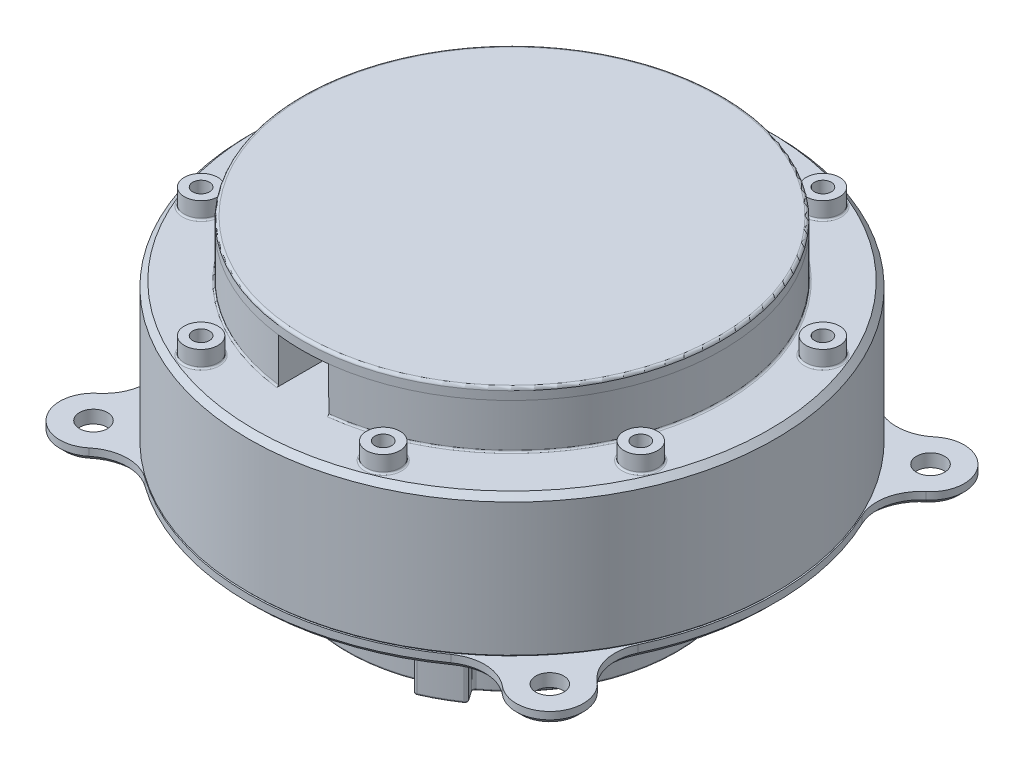
SolidWorks part; units mm, degrees
material "6061 合金"
ref_plane "前视基准面" through (0, 0, 0) normal (0, 0, 1) x (1, 0, 0)
ref_plane "上视基准面" through (0, 0, 0) normal (0, 1, 0) x (1, 0, 0)
ref_plane "右视基准面" through (0, 0, 0) normal (1, 0, 0) x (0, 0, -1)
sketch "草图1" plane through (0, 0, 0) normal (0, 1, 0) x (1, 0, 0)
  line L1 (16.264, -39.2649) -> (39.2649, -16.264) construction
  line L2 (39.2649, -16.264) -> (39.2649, 16.264) construction
  line L3 (39.2649, 16.264) -> (16.264, 39.2649) construction
  line L4 (16.264, 39.2649) -> (-16.264, 39.2649) construction
  line L5 (-16.264, 39.2649) -> (-39.2649, 16.264) construction
  line L6 (-39.2649, 16.264) -> (-39.2649, -16.264) construction
  line L7 (-39.2649, -16.264) -> (-16.264, -39.2649) construction
  line L8 (-16.264, -39.2649) -> (16.264, -39.2649) construction
  circle A0 centre (0, 0) radius 42.5 construction
  circle A1 centre (0, 0) radius 47
  circle A2 centre (0, 0) radius 39.2649 construction
  circle A3 centre (-16.264, 39.2649) radius 1.5
  circle A4 centre (16.264, 39.2649) radius 1.5
  circle A5 centre (39.2649, 16.264) radius 1.5
  circle A6 centre (39.2649, -16.264) radius 1.5
  circle A7 centre (16.264, -39.2649) radius 1.5
  circle A8 centre (-16.264, -39.2649) radius 1.5
  circle A9 centre (-39.2649, -16.264) radius 1.5
  circle A10 centre (-39.2649, 16.264) radius 1.5
  dimension "D1" = 85
  dimension "D2" = 94
  dimension "D3" = 3
extrude "凸台-拉伸1" add sketch "草图1" along normal blind 25
sketch "草图2" plane through (0, 25, 0) normal (0, 1, 0) x (1, 0, 0)
  circle A0 centre (-16.264, 39.2649) radius 3
  circle A1 centre (16.264, 39.2649) radius 1.5
  circle A2 centre (16.264, 39.2649) radius 1.5
  circle A3 centre (-16.264, 39.2649) radius 1.5
  circle A4 centre (-16.264, 39.2649) radius 1.5
  circle A5 centre (39.2649, 16.264) radius 1.5
  circle A6 centre (39.2649, 16.264) radius 1.5
  circle A7 centre (39.2649, -16.264) radius 1.5
  circle A8 centre (39.2649, -16.264) radius 1.5
  circle A9 centre (16.264, -39.2649) radius 1.5
  circle A10 centre (16.264, -39.2649) radius 1.5
  circle A11 centre (-16.264, -39.2649) radius 1.5
  circle A12 centre (-16.264, -39.2649) radius 1.5
  circle A13 centre (-39.2649, -16.264) radius 1.5
  circle A14 centre (-39.2649, -16.264) radius 1.5
  circle A15 centre (-39.2649, 16.264) radius 1.5
  circle A16 centre (-39.2649, 16.264) radius 1.5
  circle A17 centre (16.264, 39.2649) radius 3
  circle A18 centre (39.2649, 16.264) radius 3
  circle A19 centre (39.2649, -16.264) radius 3
  circle A20 centre (16.264, -39.2649) radius 3
  circle A21 centre (-16.264, -39.2649) radius 3
  circle A22 centre (-39.2649, -16.264) radius 3
  circle A23 centre (-39.2649, 16.264) radius 3
  dimension "D9" = 6
  dimension "D1" = 0
  dimension "D2" = 0
  dimension "D3" = 0
  dimension "D4" = 0
  dimension "D5" = 0
  dimension "D6" = 0
  dimension "D7" = 0
  dimension "D8" = 0
extrude "凸台-拉伸2" add sketch "草图2" along normal blind 3
sketch "草图3" plane through (0, 25, 0) normal (0, 1, 0) x (1, 0, 0)
  line L1 (-4.5, 0) -> (4.5, 0)
  line L2 (-4.5, 0) -> (-4.5, -47)
  line L3 (-4.5, -47) -> (4.5, -47)
  line L4 (4.5, 0) -> (4.5, -47)
  line L5 (-4.5, 0) -> (4.5, -47) construction
  line L6 (-4.5, -47) -> (4.5, 0) construction
  circle A0 centre (0, 0) radius 37.5
  circle A1 centre (0, 0) radius 47 construction
  point P3 (0, -23.5)
  dimension "D1" = 75
  dimension "D2" = 9
extrude "凸台-拉伸3" add sketch "草图3" along normal blind 8 contours L4 A0 L2 L1 region at (0, 25, -1.5431)
sketch "草图4" plane through (0, 33, 0) normal (0, 1, 0) x (1, 0, 0)
  circle A0 centre (0, 0) radius 37.505
  dimension "D1" = 75.01
extrude "凸台-拉伸4" add sketch "草图4" along normal blind 2
fillet "圆角1" radius 0.5 1 edges at (0, 35, 37.505)
chamfer "倒角1" distance 1 angle 45 1 edges at (0, 25, 47)
fillet "圆角2" radius 0.3 9 edges at (0, 25, -37.5) (16.264, 25, 42.2649) (39.2649, 25, 19.264) (39.2649, 25, -13.264) (16.264, 25, -36.2649) (-16.264, 25, -36.2649) (-39.2649, 25, -13.264) (-39.2649, 25, 19.264) (-16.264, 25, 42.2649)
chamfer "倒角2" distance 0.3 angle 45 1 edges at (0, 0, 47)
sketch "草图5" plane through (0, 0, 0) normal (0, -1, 0) x (1, 0, 0)
  line L0 (36.9061, 38.607) -> (44.5939, 29.393) construction
  line L1 (-40.75, 34) -> (40.75, 34) construction
  line L2 (-40.75, 34) -> (-40.75, -34) construction
  line L3 (-40.75, -34) -> (40.75, -34) construction
  line L4 (40.75, 34) -> (40.75, -34) construction
  line L5 (-40.75, 34) -> (40.75, -34) construction
  line L6 (-40.75, -34) -> (40.75, 34) construction
  line L7 (44.5939, -29.393) -> (36.9061, -38.607) construction
  line L8 (-36.9061, -38.607) -> (-44.5939, -29.393) construction
  line L9 (-44.5939, 29.393) -> (-36.9061, 38.607) construction
  circle A2 centre (16.264, -39.2649) radius 1.5
  circle A3 centre (16.264, -39.2649) radius 1.5 construction
  circle A4 centre (-16.264, -39.2649) radius 1.5
  circle A5 centre (-16.264, -39.2649) radius 1.5 construction
  circle A6 centre (39.2649, -16.264) radius 1.5
  circle A7 centre (39.2649, -16.264) radius 1.5 construction
  circle A8 centre (39.2649, 16.264) radius 1.5
  circle A9 centre (39.2649, 16.264) radius 1.5 construction
  circle A10 centre (16.264, 39.2649) radius 1.5
  circle A11 centre (16.264, 39.2649) radius 1.5 construction
  circle A12 centre (-16.264, 39.2649) radius 1.5
  circle A13 centre (-16.264, 39.2649) radius 1.5 construction
  circle A14 centre (-39.2649, 16.264) radius 1.5
  circle A15 centre (-39.2649, 16.264) radius 1.5 construction
  circle A16 centre (-39.2649, -16.264) radius 1.5
  circle A17 centre (-39.2649, -16.264) radius 1.5 construction
  circle A18 centre (40.75, 34) radius 2.5
  arc A19 (44.5939, 29.393) -> (42.5214, 20.0232) centre (49.6219, 23.3668) ccw
  circle A20 centre (40.75, -34) radius 2.5
  circle A21 centre (-40.75, 34) radius 2.5
  circle A22 centre (-40.75, -34) radius 2.5
  arc A23 (36.9061, 38.607) -> (44.5939, 29.393) centre (40.75, 34) cw
  arc A24 (27.3166, 38.2466) -> (36.9061, 38.607) centre (31.8781, 44.6332) ccw
  circle A25 centre (0, 0) radius 47 construction
  arc A26 (44.5939, -29.393) -> (36.9061, -38.607) centre (40.75, -34) cw
  arc A27 (36.9061, -38.607) -> (27.3166, -38.2466) centre (31.8781, -44.6332) ccw
  arc A28 (44.5939, -29.393) -> (42.5214, -20.0232) centre (49.6219, -23.3668) cw
  arc A29 (-44.5939, -29.393) -> (-36.9061, -38.607) centre (-40.75, -34) ccw
  arc A30 (-36.9061, -38.607) -> (-27.3166, -38.2466) centre (-31.8781, -44.6332) cw
  arc A31 (-44.5939, -29.393) -> (-42.5214, -20.0232) centre (-49.6219, -23.3668) ccw
  arc A32 (-44.5939, 29.393) -> (-36.9061, 38.607) centre (-40.75, 34) cw
  arc A33 (-44.5939, 29.393) -> (-42.5214, 20.0232) centre (-49.6219, 23.3668) cw
  arc A34 (-36.9061, 38.607) -> (-27.3166, 38.2466) centre (-31.8781, 44.6332) ccw
  arc A35 (-42.5214, 20.0232) -> (-42.5214, -20.0232) centre (0, 0) ccw
  arc A36 (-27.3166, 38.2466) -> (27.3166, 38.2466) centre (0, 0) cw
  arc A37 (-27.3166, -38.2466) -> (27.3166, -38.2466) centre (0, 0) ccw
  arc A38 (42.5214, 20.0232) -> (42.5214, -20.0232) centre (0, 0) cw
  point P0 (0, 0)
  dimension "D9" = 5
  dimension "D12" = 6
  dimension "D13" = 6
  dimension "D14" = 6
  dimension "D15" = 6
  dimension "D10" = 68
  dimension "D11" = 81.5
  dimension "D1" = 0
  dimension "D2" = 0
  dimension "D3" = 0
  dimension "D4" = 0
  dimension "D5" = 0
  dimension "D6" = 0
  dimension "D7" = 0
  dimension "D8" = 0
extrude "凸台-拉伸5" add sketch "草图5" along normal blind 2.3
sketch "草图16" plane through (0, -2.3, 0) normal (0, -1, 0) x (1, 0, 0)
  circle A0 centre (0, 0) radius 40
  dimension "D1" = 80
extrude "切除-拉伸5" cut sketch "草图16" against normal blind 1
chamfer "倒角6" distance 1 angle 45 17 edges at (0, -2.3, -40) (41.9588, -2.3, -25.0617) (47, -2.3, 0) (45.357, -2.3, -37.8439) (41.9588, -2.3, 25.0617) (32.1729, -2.3, -36.7904) (45.357, -2.3, 37.8439) (0, -2.3, -47) (32.1729, -2.3, 36.7904) (-32.1729, -2.3, -36.7904) (0, -2.3, 47) (-45.357, -2.3, -37.8439) (-32.1729, -2.3, 36.7904) (-41.9588, -2.3, -25.0617) (-45.357, -2.3, 37.8439) (-47, -2.3, 0) (-41.9588, -2.3, 25.0617)
sketch "草图6" plane through (0, -1.3, 0) normal (0, -1, 0) x (1, 0, 0)
  line L0 (0, 0) -> (0, 24.5478) construction
  line L1 (-11.25, 27.2706) -> (11.25, 27.2706) construction
  line L2 (17, 24.1091) -> (-17, 24.1091) construction
  line L3 (-17, 24.1091) -> (0, 0) construction
  line L4 (-11.25, 27.2706) -> (0, 0) construction
  line L5 (-17.2857, 24.5144) -> (-18.4384, 26.1491)
  line L6 (-12.2019, 29.5781) -> (-11.4391, 27.729)
  line L7 (17.2857, -24.5144) -> (18.4384, -26.1491)
  line L8 (11.4391, -27.729) -> (12.2019, -29.5781)
  line L9 (12.2019, 29.5781) -> (11.4391, 27.729)
  line L10 (17.2857, 24.5144) -> (18.4384, 26.1491)
  line L11 (-17.2857, -24.5144) -> (-18.4384, -26.1491)
  line L12 (-11.4391, -27.729) -> (-12.2019, -29.5781)
  circle A0 centre (0, 0) radius 29.5 construction
  circle A1 centre (0, 0) radius 27.5
  circle A2 centre (0, 0) radius 32.5 construction
  arc A3 (-18.3115, 26.8503) -> (-12.862, 29.8466) centre (0, 0) cw
  arc A4 (18.3115, -26.8503) -> (12.862, -29.8466) centre (0, 0) cw
  arc A5 (18.3115, 26.8503) -> (12.862, 29.8466) centre (0, 0) ccw
  arc A6 (-18.3115, -26.8503) -> (-12.862, -29.8466) centre (0, 0) ccw
  arc A7 (-10.7939, 27.4543) -> (10.7939, 27.4543) centre (0, 0) cw
  arc A8 (-10.7939, -27.4543) -> (10.7939, -27.4543) centre (0, 0) ccw
  arc A9 (17.3995, 23.8224) -> (17.3995, -23.8224) centre (0, 0) cw
  arc A10 (-17.3995, 23.8224) -> (-17.3995, -23.8224) centre (0, 0) ccw
  arc A11 (18.3115, 26.8503) -> (18.4384, 26.1491) centre (18.0298, 26.4372) cw
  arc A12 (12.2019, 29.5781) -> (12.862, 29.8466) centre (12.6641, 29.3874) cw
  arc A13 (11.4391, 27.729) -> (10.7939, 27.4543) centre (10.9769, 27.9197) cw
  arc A14 (17.2857, 24.5144) -> (17.3995, 23.8224) centre (17.6944, 24.2262) ccw
  arc A15 (17.2857, -24.5144) -> (17.3995, -23.8224) centre (17.6944, -24.2262) cw
  arc A16 (11.4391, -27.729) -> (10.7939, -27.4543) centre (10.9769, -27.9197) ccw
  arc A17 (-11.4391, -27.729) -> (-10.7939, -27.4543) centre (-10.9769, -27.9197) cw
  arc A18 (-17.2857, -24.5144) -> (-17.3995, -23.8224) centre (-17.6944, -24.2262) ccw
  arc A19 (-17.2857, 24.5144) -> (-17.3995, 23.8224) centre (-17.6944, 24.2262) cw
  arc A20 (-18.4384, 26.1491) -> (-18.3115, 26.8503) centre (-18.0298, 26.4372) cw
  arc A21 (-12.2019, 29.5781) -> (-12.862, 29.8466) centre (-12.6641, 29.3874) ccw
  arc A22 (-11.4391, 27.729) -> (-10.7939, 27.4543) centre (-10.9769, 27.9197) ccw
  arc A23 (-18.4384, -26.1491) -> (-18.3115, -26.8503) centre (-18.0298, -26.4372) ccw
  arc A24 (-12.862, -29.8466) -> (-12.2019, -29.5781) centre (-12.6641, -29.3874) ccw
  arc A25 (12.2019, -29.5781) -> (12.862, -29.8466) centre (12.6641, -29.3874) ccw
  arc A26 (18.4384, -26.1491) -> (18.3115, -26.8503) centre (18.0298, -26.4372) cw
  point P35 (18.7288, 26.5609)
  point P38 (12.3941, 30.0439)
  point P47 (17, -24.1091)
  point P50 (11.25, -27.2706)
  point P53 (-11.25, -27.2706)
  point P56 (-17, -24.1091)
  point P62 (-18.7288, 26.5609)
  point P65 (-12.3941, 30.0439)
  point P71 (-18.7288, -26.5609)
  point P74 (-12.3941, -30.0439)
  point P77 (12.3941, -30.0439)
  point P80 (18.7288, -26.5609)
  dimension "D1" = 59
  dimension "D2" = 55
  dimension "D5" = 65
  dimension "D6" = 0.5
  dimension "D7" = 0.5
  dimension "D3" = 22.5
  dimension "D4" = 34
extrude "凸台-拉伸6" add sketch "草图6" along normal blind 16.5
sketch "草图7" plane through (0, -1.3, 0) normal (0, -1, 0) x (1, 0, 0)
  circle A0 centre (0, 0) radius 22
  circle A1 centre (0, 0) radius 27.5
  circle A3 centre (0, 0) radius 27.5 construction
  dimension "D1" = 44
extrude "凸台-拉伸7" add sketch "草图7" along normal offset from surface (7.5 mm away) 9 up to face at (0, -17.8, 0)
sketch "草图8" plane through (0, -1.3, 0) normal (0, -1, 0) x (1, 0, 0)
  circle A0 centre (0, 0) radius 21
  dimension "D1" = 42
extrude "凸台-拉伸8" add sketch "草图8" along normal offset from surface (7 mm away) 9.5 up to face at (0, -17.8, 0)
sketch "草图9" plane through (0, -8.3, 0) normal (0, -1, 0) x (1, 0, 0)
  circle A0 centre (0, 0) radius 20
  dimension "D1" = 40
extrude "凸台-拉伸9" add sketch "草图9" along normal blind 10
sketch "草图10" plane through (0, -18.3, 0) normal (0, -1, 0) x (1, 0, 0)
  circle A0 centre (0, 0) radius 9.75
  dimension "D1" = 19.5
extrude "切除-拉伸1" cut sketch "草图10" against normal blind 5.5
sketch "草图11" plane through (0, -18.3, 0) normal (0, -1, 0) x (1, 0, 0)
  line L0 (0, 12.9615) -> (0, 15.9687)
  line L1 (7.2321, 10.7562) -> (8.9101, 13.2518)
  line L2 (5.6991, -11.6413) -> (7.0214, -14.3423)
  line L3 (11.225, -6.4807) -> (13.8293, -7.9844)
  line L4 (-12.9312, 0.8851) -> (-15.9314, 1.0904)
  line L5 (-11.225, -6.4807) -> (-13.8293, -7.9844)
  circle A0 centre (0, 0) radius 12 construction
  circle A1 centre (0, 0) radius 17 construction
  arc A2 (0.9231, 11.9644) -> (5.9098, 10.4439) centre (0, 0) cw
  arc A3 (1.0625, 16.9668) -> (8.5852, 14.6729) centre (0, 0) cw
  arc A4 (8.9101, 13.2518) -> (8.5852, 14.6729) centre (8.0802, 13.8098) ccw
  arc A5 (5.9098, 10.4439) -> (7.2321, 10.7562) centre (6.4023, 11.3142) ccw
  arc A6 (0.9231, 11.9644) -> (0, 12.9615) centre (1, 12.9615) cw
  arc A7 (0, 15.9687) -> (1.0625, 16.9668) centre (1, 15.9687) cw
  arc A8 (14.1624, -9.4035) -> (8.4145, -14.7715) centre (0, 0) cw
  arc A9 (13.8293, -7.9844) -> (14.1624, -9.4035) centre (13.3293, -8.8504) cw
  arc A10 (7.0214, -14.3423) -> (8.4145, -14.7715) centre (7.9195, -13.9026) ccw
  arc A11 (6.0898, -10.34) -> (5.6991, -11.6413) centre (6.5973, -11.2016) ccw
  arc A12 (9.9, -6.7816) -> (6.0898, -10.34) centre (0, 0) cw
  arc A13 (9.9, -6.7816) -> (11.225, -6.4807) centre (10.725, -7.3468) cw
  arc A14 (-15.2249, -7.5632) -> (-16.9997, 0.0986) centre (0, 0) cw
  arc A15 (-13.8293, -7.9844) -> (-15.2249, -7.5632) centre (-14.3293, -7.1183) cw
  arc A16 (-15.9314, 1.0904) -> (-16.9997, 0.0986) centre (-15.9997, 0.0928) ccw
  arc A17 (-11.9995, -0.1039) -> (-12.9312, 0.8851) centre (-12.9995, -0.1126) ccw
  arc A18 (-10.8231, -5.1828) -> (-11.9995, -0.1039) centre (0, 0) cw
  arc A19 (-10.8231, -5.1828) -> (-11.225, -6.4807) centre (-11.725, -5.6147) cw
  point P12 (9.4855, 14.1076)
  point P15 (6.6956, 9.9583)
  point P18 (0, 12)
  point P21 (0, 17)
  point P48 (0, 0)
  dimension "D1" = 24
  dimension "D2" = 34
  dimension "D4" = 1
  dimension "D3" = 7
  dimension "D5" = 3
extrude "切除-拉伸2" cut sketch "草图11" against normal blind 5.6
sketch "草图12" plane through (0, -18.3, 0) normal (0, -1, 0) x (1, 0, 0)
  line L0 (1.0625, 16.9668) -> (8.5852, 14.6729) construction
  line L1 (-3.0618, 13.2177) -> (-12.9778, 3.9573) construction
  line L2 (-12.9778, 3.9573) -> (-9.916, -9.2605) construction
  line L3 (-9.916, -9.2605) -> (3.0618, -13.2177) construction
  line L4 (3.0618, -13.2177) -> (12.9778, -3.9573) construction
  line L5 (12.9778, -3.9573) -> (9.916, 9.2605) construction
  line L6 (9.916, 9.2605) -> (-3.0618, 13.2177) construction
  circle A0 centre (0, 0) radius 11.75 construction
  circle A1 centre (-3.0618, 13.2177) radius 1.5
  circle A2 centre (9.916, 9.2605) radius 1.5
  circle A3 centre (12.9778, -3.9573) radius 1.5
  circle A4 centre (3.0618, -13.2177) radius 1.5
  circle A5 centre (-9.916, -9.2605) radius 1.5
  circle A6 centre (-12.9778, 3.9573) radius 1.5
  dimension "D2" = 3
  dimension "D1" = 23.5
extrude "切除-拉伸3" cut sketch "草图12" against normal blind 6
sketch "草图13" plane through (0, -18.3, 0) normal (0, -1, 0) x (1, 0, 0)
  line L0 (-3.0618, 13.2177) -> (-2.708, 11.6904) construction
  line L1 (-4.0415, -13.2539) -> (9.4575, -10.127) construction
  line L2 (9.4575, -10.127) -> (13.499, 3.127) construction
  line L3 (13.499, 3.127) -> (4.0415, 13.2539) construction
  line L4 (4.0415, 13.2539) -> (-9.4575, 10.127) construction
  line L5 (-9.4575, 10.127) -> (-13.499, -3.127) construction
  line L6 (-13.499, -3.127) -> (-4.0415, -13.2539) construction
  circle A0 centre (0, 0) radius 12 construction
  circle A1 centre (-9.4575, 10.127) radius 2
  circle A2 centre (13.499, 3.127) radius 2
  circle A3 centre (-4.0415, -13.2539) radius 2
  dimension "D2" = 4
  dimension "D1" = 24
extrude "凸台-拉伸10" add sketch "草图13" along normal blind 2.6
chamfer "倒角3" distance 0.5 angle 45 1 edges at (0, -18.3, -20)
chamfer "倒角4" distance 0.2 angle 45 34 edges at (0, -18.3, -9.75) (6.3602, -18.3, -12.9918) (7.6251, -18.3, -14.8582) (5.6395, -18.3, -10.9141) (11.6031, -18.3, -12.4245) (8.1904, -18.3, -8.7702) (14.3029, -18.3, -8.6219) (10.5035, -18.3, -6.3716) (12.5271, -18.3, -7.2326) (0.3153, -18.3, 16.6976) (0, -18.3, 14.4651) (4.9583, -18.3, 16.2608) (0.2662, -18.3, 12.2821) (9.0551, -18.3, 14.0326) (3.5, -18.3, 11.4782) (8.0711, -18.3, 12.004) (6.6321, -18.3, 10.341) (-16.5615, -18.3, -3.8364) (-14.6182, -18.3, -8.0757) (-16.6801, -18.3, 0.8256) (-12.5271, -18.3, -7.2326) (-14.4313, -18.3, 0.9878) (-10.7697, -18.3, -5.9105) (-12.2716, -18.3, 0.5731) (-11.6904, -18.3, -2.708) (13.499, -20.9, 1.127) (-4.0415, -20.9, -15.2539) (-9.4575, -20.9, 8.127) (-12.9778, -18.3, 2.4573) (-9.916, -18.3, -10.7605) (12.9778, -18.3, -5.4573) (9.916, -18.3, 7.7605) (-3.0618, -18.3, 11.7177) (3.0618, -18.3, -14.7177)
fillet "圆角4" radius 0.3 67 edges at (0, -8.8, 27.5) (0, -8.3, -20) (-17.201, -17.8, 24.1451) (-17.8621, -17.8, 25.3317) (-18.5218, -17.8, 26.5263) (-15.6586, -17.8, 28.4791) (-12.4757, -17.8, 29.8506) (-11.8205, -17.8, 28.6535) (-11.1727, -17.8, 27.4596) (0, -17.8, 29.5) (11.1727, -17.8, 27.4596) (11.8205, -17.8, 28.6535) (12.4757, -17.8, 29.8506) (15.6586, -17.8, 28.4791) (18.5218, -17.8, 26.5263) (17.8621, -17.8, 25.3317) (17.201, -17.8, 24.1451) (29.5, -17.8, 0) (17.201, -17.8, -24.1451) (17.8621, -17.8, -25.3317) (18.5218, -17.8, -26.5263) (15.6586, -17.8, -28.4791) (12.4757, -17.8, -29.8506) (11.8205, -17.8, -28.6535) (11.1727, -17.8, -27.4596) (0, -17.8, -29.5) (-11.1727, -17.8, -27.4596) (-11.8205, -17.8, -28.6535) (-12.4757, -17.8, -29.8506) (-15.6586, -17.8, -28.4791) (-18.5218, -17.8, -26.5263) (-17.8621, -17.8, -25.3317) (-17.201, -17.8, -24.1451) (-17.201, -1.3, 24.1451) (-17.8621, -1.3, 25.3317) (-18.5218, -1.3, 26.5263) (-15.6586, -1.3, 28.4791) (-12.4757, -1.3, 29.8506) (-11.8205, -1.3, 28.6535) (-11.1727, -1.3, 27.4596) (0, -1.3, 29.5) (11.1727, -1.3, 27.4596) (11.8205, -1.3, 28.6535) (12.4757, -1.3, 29.8506) (15.6586, -1.3, 28.4791) (18.5218, -1.3, 26.5263) (17.8621, -1.3, 25.3317) (17.201, -1.3, 24.1451) (29.5, -1.3, 0) (17.201, -1.3, -24.1451) (17.8621, -1.3, -25.3317) (18.5218, -1.3, -26.5263) (15.6586, -1.3, -28.4791) (12.4757, -1.3, -29.8506) (11.8205, -1.3, -28.6535) (11.1727, -1.3, -27.4596) (0, -1.3, -29.5) (-11.1727, -1.3, -27.4596) (-11.8205, -1.3, -28.6535) (-12.4757, -1.3, -29.8506) (-15.6586, -1.3, -28.4791) (-18.5218, -1.3, -26.5263) (-17.8621, -1.3, -25.3317) (-17.201, -1.3, -24.1451) (0, -17.8, -27.5) (-29.5, -17.8, 0) (-29.5, -1.3, 0)
sketch "草图15" plane through (0, -1.3, 0) normal (0, -1, 0) x (1, 0, 0)
  circle A0 centre (0, 0) radius 19.25
  dimension "D1" = 38.5
extrude "切除-拉伸4" cut sketch "草图15" against normal up to surface (26.3 mm away) and the other way blind 6 up to face at (16.264, 25, 42.5649)
